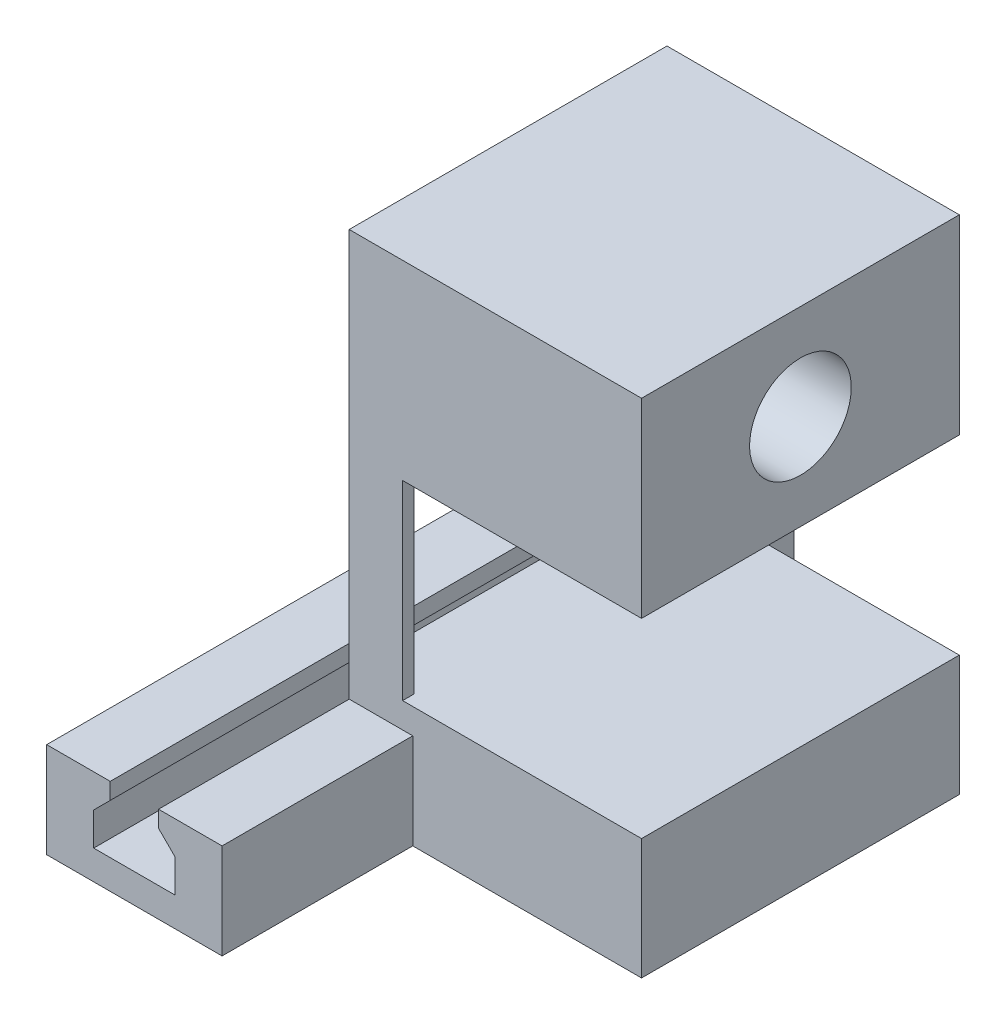
SolidWorks part; units mm, degrees
ref_plane "Plan de face" through (0, 0, 0) normal (0, 0, 1) x (1, 0, 0)
ref_plane "Plan de dessus" through (0, 0, 0) normal (0, 1, 0) x (1, 0, 0)
ref_plane "Plan de droite" through (0, 0, 0) normal (1, 0, 0) x (0, 0, -1)
sketch "Esquisse1" plane through (0, 0, 0) normal (0, 0, 1) x (1, 0, 0)
  line L0 (0, 0) -> (0, -5.2499) construction
  line L5 (0, 0) -> (0, 6.7252) construction
  line L6 (0, 0) -> (7.76, 0) construction
  line L7 (0, 0) -> (-6.4576, 0) construction
  line L8 (-3.2, 0) -> (3.2, 0)
  line L9 (-3.2, 0) -> (-3.2, 2.6)
  line L10 (3.2, 0) -> (3.2, 2.6)
  line L12 (-1.9, 5.2) -> (-1.9, 3.9)
  line L13 (1.9, 5.2) -> (1.9, 3.9)
  line L14 (-3.2, 2.6) -> (-1.9, 3.9)
  line L15 (1.9, 3.9) -> (3.2, 2.6)
  line L16 (-1.9, 5.2) -> (-6.9, 5.2)
  line L17 (-6.9, 5.2) -> (-6.9, -2.3)
  line L18 (-6.9, -2.3) -> (6.9, -2.3)
  line L19 (6.9, -2.3) -> (6.9, 5.2)
  line L20 (6.9, 5.2) -> (1.9, 5.2)
  point P10 (0, 0)
  point P15 (0, 5.2)
  dimension "D1" = 6.4
  dimension "D2" = 2.6
  dimension "D3" = 2.6
  dimension "D4" = 3.8
  dimension "D5" = 1.3
  dimension "D6" = 1.3
  dimension "D7" = 1.3
  dimension "D8" = 5
  dimension "D9" = 5
  dimension "D10" = 7.5
extrude "Boss.-Extru.1" add sketch "Esquisse1" along normal blind 45
sketch "Esquisse6" plane through (6.9, 0, 0) normal (1, 0, 0) x (0, 0, -1)
  line L0 (-45, -2.3) -> (0, -2.3) construction
  line L1 (-30, -2.3) -> (-5, -2.3)
  line L2 (-30, -2.3) -> (-30, 5.2)
  line L3 (-30, 5.2) -> (-5, 5.2)
  line L4 (-5, -2.3) -> (-5, 5.2)
  line L5 (-45, 5.2) -> (0, 5.2) construction
  line L6 (0, -2.3) -> (0, 5.2) construction
  dimension "D1" = 5
  dimension "D2" = 25
extrude "Boss.-Extru.6" add sketch "Esquisse6" along normal blind 18
sketch "Esquisse7" plane through (0, 5.2, 0) normal (0, 1, 0) x (1, 0, 0)
  line L0 (1.9, -45) -> (1.9, 0) construction
  line L1 (24.9, -30) -> (1.9, -30)
  line L2 (24.9, -30) -> (24.9, -5)
  line L3 (24.9, -5) -> (1.9, -5)
  line L4 (1.9, -30) -> (1.9, -5)
  dimension "D1" = 25
extrude "Boss.-Extru.7" add sketch "Esquisse7" along normal blind 2
sketch "Esquisse8" plane through (0, 7.2, 0) normal (0, 1, 0) x (1, 0, 0)
  line L1 (1.9, -30) -> (6.1, -30)
  line L2 (1.9, -30) -> (1.9, -29.1)
  line L3 (1.9, -29.1) -> (6.1, -29.1)
  line L4 (6.1, -30) -> (6.1, -29.1)
  line L5 (1.9, -5) -> (6.1, -5)
  line L6 (1.9, -5) -> (1.9, -5.9)
  line L7 (1.9, -5.9) -> (6.1, -5.9)
  line L8 (6.1, -5) -> (6.1, -5.9)
  dimension "D1" = 4.2
  dimension "D2" = 4.2
  dimension "D3" = 0.9
  dimension "D4" = 0.9
extrude "Boss.-Extru.8" add sketch "Esquisse8" along normal blind 20
sketch "Esquisse9" plane through (0, 27.2, 0) normal (0, 1, 0) x (1, 0, 0)
  line L1 (1.9, -5) -> (24.9, -5)
  line L2 (1.9, -5) -> (1.9, -30)
  line L3 (1.9, -30) -> (24.9, -30)
  line L4 (24.9, -5) -> (24.9, -30)
extrude "Boss.-Extru.9" add sketch "Esquisse9" against normal blind 5 and the other way blind 10
sketch "Esquisse10" plane through (24.9, 0, 0) normal (1, 0, 0) x (0, 0, -1)
  line L0 (-30, 37.2) -> (-5, 22.2) construction
  circle A0 centre (-17.5, 29.7) radius 4
  dimension "D1" = 8
extrude "Enlèv. mat.-Extru.1" cut sketch "Esquisse10" against normal through all
